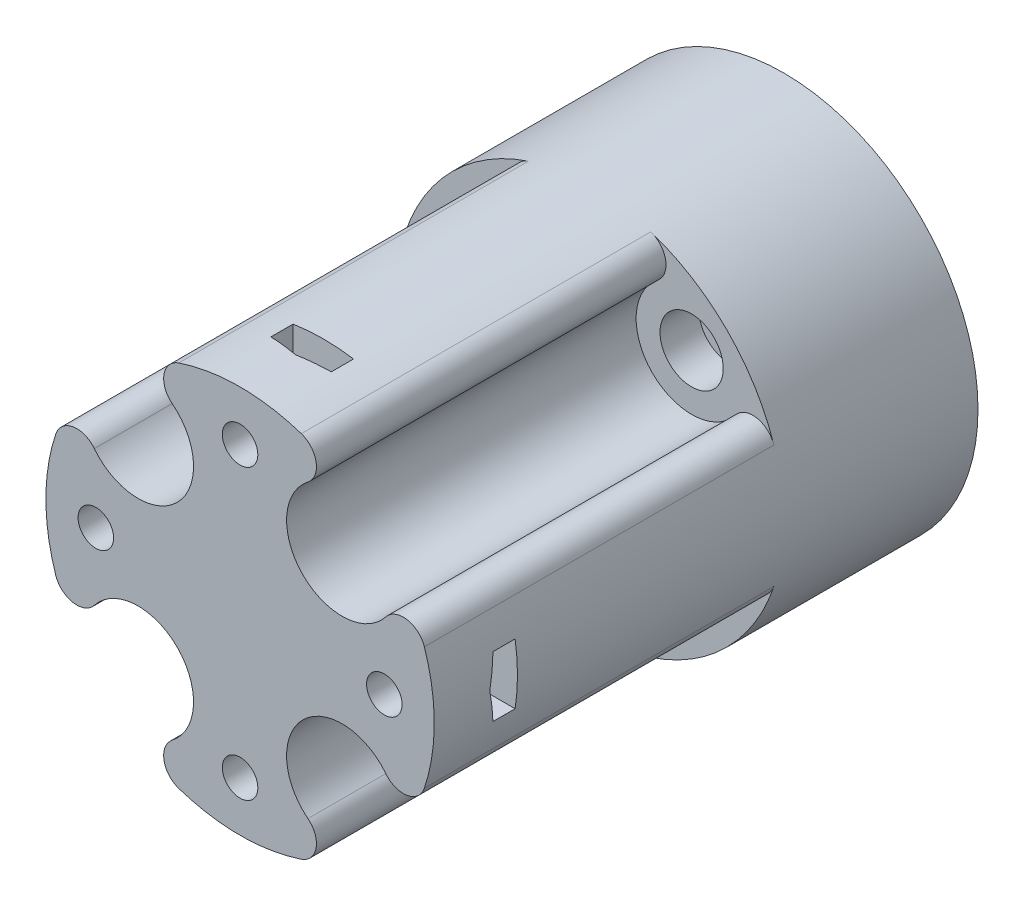
SolidWorks part; units mm, degrees
ref_plane "Front Plane" through (0, 0, 0) normal (1, 0, 0) x (0, 1, 0)
ref_plane "Top Plane" through (0, 0, 0) normal (0, 0, 1) x (0, 1, 0)
ref_plane "Right Plane" through (0, 0, 0) normal (0, 1, 0) x (-1, 0, 0)
sketch "Sketch1" plane through (0, 0, 0) normal (0, 0, 1) x (0, 1, 0)
  line L0 (0, 0) -> (9.1924, 9.1924) construction
  circle A0 centre (0, 0) radius 17.5
  circle A1 centre (0, 0) radius 13 construction
  circle A2 centre (9.1924, 9.1924) radius 1.6
  circle A3 centre (9.1924, 9.1924) radius 2.85
  circle A4 centre (9.1924, -9.1924) radius 2.85
  circle A5 centre (9.1924, -9.1924) radius 1.6
  circle A6 centre (-9.1924, -9.1924) radius 2.85
  circle A7 centre (-9.1924, -9.1924) radius 1.6
  circle A8 centre (-9.1924, 9.1924) radius 2.85
  circle A9 centre (-9.1924, 9.1924) radius 1.6
  circle A10 centre (0, 0) radius 22.5
  point P19 (0, 0)
  dimension "D1" = 35
  dimension "D2" = 26
  dimension "D3" = 3.2
  dimension "D4" = 5.7
  dimension "D6" = 45
  dimension "D5" = 4
extrude "Boss-Extrude1" add sketch "Sketch1" along normal blind 48 contours A0 A8 A6 A4 A3 region at (0, 0, 0)
extrude "Boss-Extrude3" add sketch "Sketch1<4>" against normal blind 1 contours A0 A8 A6 A4 A3 region at (0, 0, 0)
sketch "Sketch1<4>" plane through (0, 0, 0) normal (0, 0, 1) x (0, 1, 0) same geometry as "Sketch1"
extrude "Boss-Extrude2" add sketch "Sketch1<3>" along normal blind 13 and the other way up to surface (1 mm away) contours A6 A7 | A8 A9 | A4 A5 | A3 A2 region at (-9.1924, 6.423, 0) region at (9.1924, 6.423, 0) region at (9.1924, -11.9618, 0) region at (-9.1924, -11.9618, 0) other way up to face at (-6.3424, -9.1924, -1)
sketch "Sketch1<3>" plane through (0, 0, 0) normal (0, 0, 1) x (0, 1, 0) same geometry as "Sketch1"
sketch "Sketch2" plane through (0, 0, 48) normal (0, 0, 1) x (1, 0, 0)
  circle A0 centre (-9.1924, 9.1924) radius 5
  circle A1 centre (9.1924, 9.1924) radius 5
  circle A2 centre (9.1924, -9.1924) radius 5
  circle A3 centre (-9.1924, -9.1924) radius 5
  dimension "D1" = 10
  dimension "D2" = 2
  dimension "D3" = 2
extrude "Cut-Extrude1" cut sketch "Sketch2" against normal offset from surface (31.5 mm away) 3.5 contours A3 A0 | A0 A2 | A1 | A2 A3 region at (-9.1924, 9.1924, 48) region at (9.1924, 9.1924, 48) region at (9.1924, -9.1924, 48) region at (-9.1924, -9.1924, 48) up to face at (10.7924, 9.1924, 13)
fillet "Fillet1" radius 2 8 edges at (14.0286, 10.4618, 32.25) (-14.0286, 10.4618, 32.25) (-10.4618, 14.0286, 32.25) (10.4618, 14.0286, 32.25) (14.0286, -10.4618, 32.25) (10.4618, -14.0286, 32.25) (-10.4618, -14.0286, 32.25) (-14.0286, -10.4618, 32.25)
sketch "Sketch3" plane through (0, 0, 48) normal (0, 0, 1) x (1, 0, 0)
  line L0 (-2.7251, 15.7252) -> (-2.7251, 17.2865)
  line L2 (-2.7251, 15.7252) -> (-2.7251, 10.2749)
  line L3 (-2.7251, 10.2749) -> (2.7249, 10.2749)
  line L4 (2.7249, 15.7249) -> (2.7249, 10.2749)
  line L5 (-2.7251, 15.7252) -> (2.7249, 10.2749) construction
  line L6 (-2.7251, 10.2749) -> (2.7249, 15.7249) construction
  line L7 (2.7249, 15.7249) -> (2.7249, 17.2865)
  line L8 (15.7249, -2.7249) -> (10.2749, -2.7249)
  line L9 (10.2749, 2.7251) -> (10.2749, -2.7249)
  line L10 (15.7252, 2.7251) -> (10.2749, 2.7251)
  line L11 (15.7252, 2.7251) -> (17.2865, 2.7251)
  line L12 (15.7249, -2.7249) -> (17.2865, -2.7249)
  line L13 (-2.7249, -15.7249) -> (-2.7249, -10.2749)
  line L14 (2.7251, -10.2749) -> (-2.7249, -10.2749)
  line L15 (2.7251, -15.7252) -> (2.7251, -10.2749)
  line L16 (2.7251, -15.7252) -> (2.7251, -17.2865)
  line L17 (-2.7249, -15.7249) -> (-2.7249, -17.2865)
  line L18 (-15.7249, 2.7249) -> (-10.2749, 2.7249)
  line L19 (-10.2749, -2.7251) -> (-10.2749, 2.7249)
  line L20 (-15.7252, -2.7251) -> (-10.2749, -2.7251)
  line L21 (-15.7252, -2.7251) -> (-17.2865, -2.7251)
  line L22 (-15.7249, 2.7249) -> (-17.2865, 2.7249)
  circle A0 centre (0, 0) radius 13 construction
  circle A2 centre (0, 13) radius 1.6
  circle A3 centre (0, 0) radius 17.5 construction
  arc A4 (-2.7251, 17.2865) -> (2.7249, 17.2865) centre (0, 0) cw
  arc A5 (17.2865, 2.7251) -> (17.2865, -2.7249) centre (0, 0) cw
  circle A6 centre (13, 0) radius 1.6
  arc A7 (2.7251, -17.2865) -> (-2.7249, -17.2865) centre (0, 0) cw
  circle A8 centre (0, -13) radius 1.6
  arc A9 (-17.2865, -2.7251) -> (-17.2865, 2.7249) centre (0, 0) cw
  circle A10 centre (-13, 0) radius 1.6
  point P41 (0, 0)
  dimension "D1" = 26
  dimension "D2" = 3.2
  dimension "D3" = 5.45
  dimension "D4" = 5.45
  dimension "D5" = 4
extrude "Cut-Extrude2" cut sketch "Sketch3" against normal blind 2.5 from offset 5 offset against normal yes
extrude "Cut-Extrude3" cut sketch "Sketch3<2>" against normal blind 10 contours A10 | A2 | A6 | A8 region at (0, 13, 48) region at (13, 0, 48) region at (0, -13, 48) region at (-13, 0, 48)
sketch "Sketch3<2>" plane through (0, 0, 48) normal (0, 0, 1) x (1, 0, 0) same geometry as "Sketch3"
chamfer "Chamfer1" distance 2.75 distance2 0.5 8 edges at (-13.7807, -2.7251, 43) (-2.7251, 13.7807, 43) (2.7249, 13.7807, 43) (13.7807, 2.7251, 43) (13.7807, -2.7249, 43) (2.7251, -13.7807, 43) (-2.7249, -13.7807, 43) (-13.7807, 2.7249, 43) first distance on face at (-14.6, 0, 43) first distance on face at (-1.6, 13, 43) first distance on face at (11.4, 0, 43) first distance on face at (-1.6, -13, 43)
